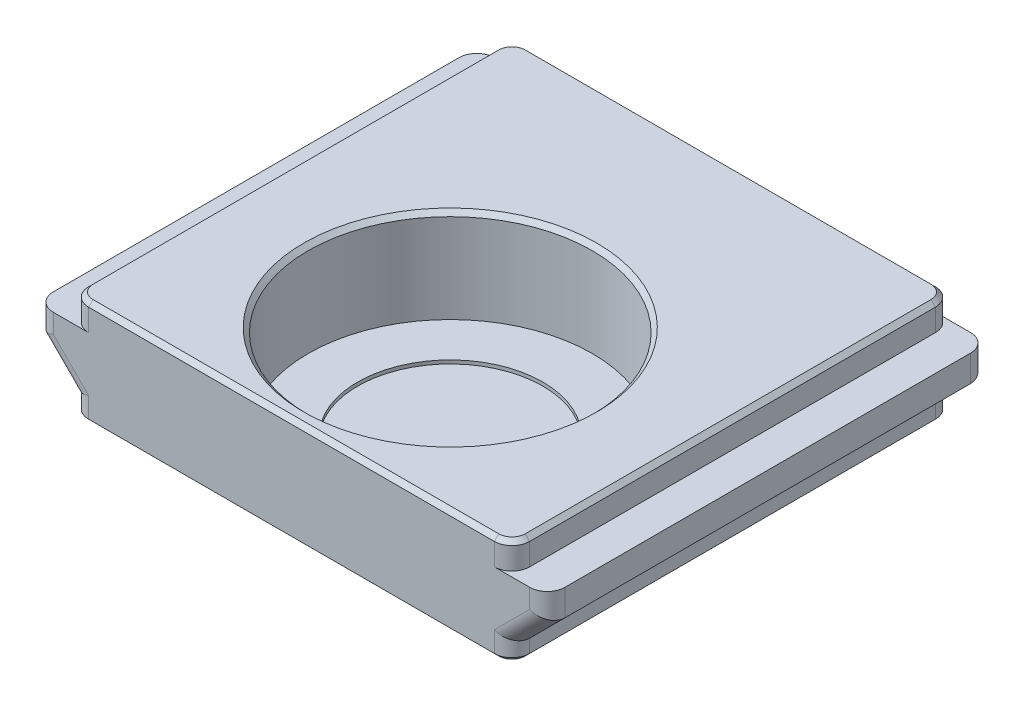
SolidWorks part; units mm, degrees
ref_plane "Front Plane" through (0, 0, 0) normal (0, 0, 1) x (1, 0, 0)
ref_plane "Top Plane" through (0, 0, 0) normal (0, 1, 0) x (1, 0, 0)
ref_plane "Right Plane" through (0, 0, 0) normal (1, 0, 0) x (0, 0, -1)
sketch "Sketch1" plane through (0, 0, 0) normal (0, 1, 0) x (1, 0, 0)
  line L1 (-12.5, -12.5) -> (12.5, -12.5)
  line L2 (-12.5, -12.5) -> (-12.5, 12.5)
  line L3 (-12.5, 12.5) -> (12.5, 12.5)
  line L4 (12.5, -12.5) -> (12.5, 12.5)
  line L5 (-12.5, -12.5) -> (12.5, 12.5) construction
  line L6 (-12.5, 12.5) -> (12.5, -12.5) construction
  point P0 (0, 0)
  dimension "D1" = 25
  dimension "D2" = 25
extrude "Boss-Extrude1" add sketch "Sketch1" along normal blind 6
sketch "Sketch2" plane through (0, 6, 0) normal (0, 1, 0) x (1, 0, 0)
  line L0 (0, -3.5) -> (0, -12.5) construction
  line L1 (-12.5, -12.5) -> (12.5, -12.5) construction
  circle A0 centre (0, -3.5) radius 8.05
  dimension "D1" = 16.1
  dimension "D2" = 9
extrude "Cut-Extrude1" cut sketch "Sketch2" against normal blind 5.5
sketch "Sketch4" plane through (0, 0, 12.5) normal (0, 0, 1) x (1, 0, 0)
  line L0 (0, 0) -> (0, 6) construction
  line L1 (-12.5, 6) -> (12.5, 6) construction
  line L2 (0, 3) -> (19.1176, 3) construction
  line L3 (12.5, 4.5) -> (14.5, 4.5)
  line L4 (12.5, 6) -> (12.5, 0) construction
  line L5 (14.5, 4.5) -> (14.5, 3)
  line L6 (14.5, 3) -> (12.5, 1)
  line L7 (12.5, 1) -> (12.5, 4.5)
  line L9 (-12.5, 1) -> (-12.5, 4.5)
  line L10 (-14.5, 3) -> (-12.5, 1)
  line L11 (-14.5, 4.5) -> (-14.5, 3)
  line L12 (-12.5, 4.5) -> (-14.5, 4.5)
  line L13 (-12.5, 0) -> (12.5, 0) construction
  dimension "D1" = 1.5
  dimension "D2" = 1
  dimension "D3" = 45
  dimension "D4" = 2
extrude "Boss-Extrude2" add sketch "Sketch4" against normal up to surface (25 mm away) up to face at (0, 3, -12.5)
sketch "Sketch5" plane through (0, 0, -12.5) normal (0, 0, -1) x (-1, 0, 0)
  line L0 (0, 0) -> (0, 6) construction
  line L1 (-12.5, 6) -> (12.5, 6) construction
  circle A0 centre (0, 3) radius 2.2
  dimension "D1" = 4.4
extrude "Cut-Extrude3" cut sketch "Sketch5" against normal blind 7.5
sketch "Sketch6" plane through (0, 0.5, 0) normal (0, 1, 0) x (1, 0, 0)
  circle A0 centre (0, -3.5) radius 5.25
  circle A1 centre (0, -3.5) radius 8.05
  circle A2 centre (0, -3.5) radius 8.05 construction
  dimension "D1" = 10.5
extrude "Boss-Extrude3" add sketch "Sketch6" along normal blind 0.2
fillet "Fillet1" radius 1 16 edges at (-13.5, 2, 12.5) (13.5, 2, 12.5) (13.5, 2, -12.5) (-13.5, 2, -12.5) (12.5, 0.5, 12.5) (14.5, 3.75, 12.5) (-14.5, 3.75, 12.5) (-12.5, 0.5, 12.5) (-12.5, 0.5, -12.5) (-14.5, 3.75, -12.5) (12.5, 5.25, 12.5) (-12.5, 5.25, 12.5) (-12.5, 5.25, -12.5) (12.5, 0.5, -12.5) (14.5, 3.75, -12.5) (12.5, 5.25, -12.5)
chamfer "Chamfer1" distance 0.5 angle 45 1 edges at (-2.2, 3, -12.5)
chamfer "Chamfer2" distance 0.25 angle 45 17 edges at (0, 0, -12.5) (-12.5, 0, 0) (0, 0, 12.5) (12.5, 0, 0) (0, 6, 12.5) (-12.5, 6, 0) (0, 6, -12.5) (12.5, 6, 0) (0, 6, 11.55) (12.2071, 0, -12.2071) (-12.2071, 0, -12.2071) (-12.2071, 0, 12.2071) (12.2071, 0, 12.2071) (-12.2071, 6, 12.2071) (-12.2071, 6, -12.2071) (12.2071, 6, -12.2071) (12.2071, 6, 12.2071)
